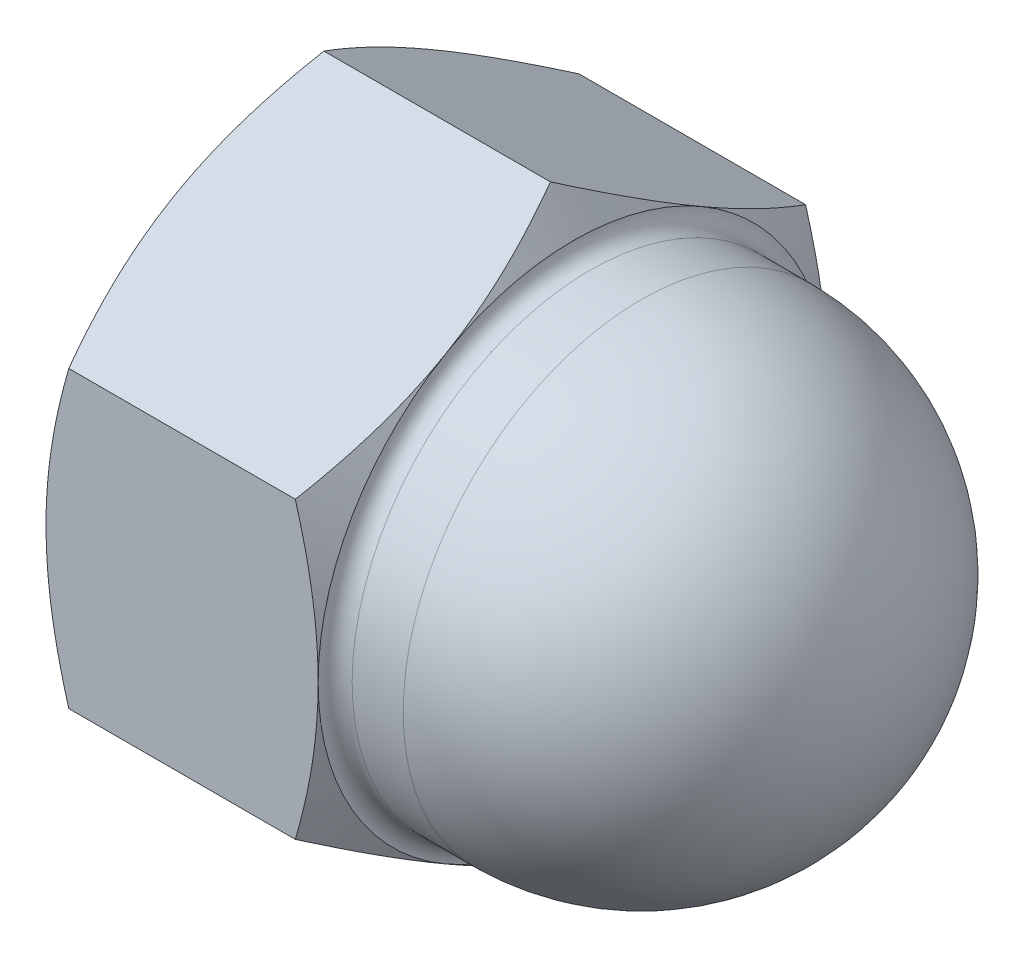
SolidWorks part; units mm, degrees
extrude "BaseNut" add sketch "BaseNutSke" along normal blind 16
sketch "BaseNutSke" plane through (0, 0, 0) normal (1, 0, 0) x (0, 0, -1)
  line L6 (15, 8.6603) -> (15, -8.6603)
  line L7 (-15, 8.6603) -> (-15, -8.6603)
  line L8 (15, 8.6603) -> (0, 17.3205)
  line L9 (0, 17.3205) -> (-15, 8.6603)
  line L10 (-15, -8.6603) -> (0, -17.3205)
  line L11 (0, -17.3205) -> (15, -8.6603)
  dimension "D4" = 60
  dimension "D1" = 120
  dimension "D2" = 15
  dimension "D3" = 15
  dimension "Width_flats" = 30
revolve "DoubleChamfer" cut sketch "Sketch4" angle 360 about L10 other way angle 118
sketch "Sketch4" plane through (0, 0, 0) normal (0, 0, 1) x (1, 0, 0)
  line L0 (0, 15) -> (2.7831, 19.8205)
  line L1 (16, 15) -> (13.2169, 19.8205)
  line L2 (2.7831, 19.8205) -> (13.2169, 19.8205)
  line L3 (16, 15) -> (18, 15)
  line L4 (18, 15) -> (18, 30)
  line L5 (18, 30) -> (-2, 30)
  line L6 (0, 15) -> (-2, 15)
  line L7 (-2, 15) -> (-2, 30)
  line L8 (16, 17.3205) -> (16, 8.6603) construction
  line L9 (0, 17.3205) -> (0, 8.6603) construction
  line L10 (0, 0) -> (57.15, 0) construction
  line L11 (16, 17.3205) -> (0, 17.3205) construction
  point P17 (16, 15)
  dimension "D1" = 30
  dimension "D2" = 30
  dimension "D3" = 2
  dimension "D4" = 2
  dimension "D5" = 2.5
  dimension "D6" = 15
  dimension "D7" = 15
revolve "TapDrill" cut sketch "TapDriSke"
sketch "TapDriSke" plane through (0, 0, 0) normal (0, 0, 1) x (1, 0, 0)
  line L0 (0, 0) -> (44.45, 0) construction
  line L1 (0, 8.75) -> (23, 8.75)
  line L2 (0, 12.9904) -> (0, 0) construction
  line L3 (23, 8.75) -> (28.2575, 0)
  line L4 (0, 0) -> (63.5, 0) construction
  line L5 (28.2575, 0) -> (0, 0)
  line L6 (0, 0) -> (0, 8.75)
  line L7 (23, -8.75) -> (28.2575, 0) construction
  line L8 (0, -8.75) -> (23, -8.75) construction
  line L9 (2.5, 6.35) -> (2.5, 3.175) construction
  dimension "Drill_depth" = 23
cosmetic thread "ThreadCosmetic" [suppressed]
revolve "EndChamfer" cut sketch "EndChamferSketch" angle 360 about L4
sketch "EndChamferSketch" plane through (0, 0, 0) normal (0, 0, 1) x (1, 0, 0)
  line L0 (-0.0254, 10) -> (0.0254, 10)
  line L1 (0.0254, 10) -> (0.9882, 8.625)
  line L2 (0.9882, 8.625) -> (-0.0254, 8.625)
  line L3 (-0.0254, 8.625) -> (-0.0254, 10)
  line L4 (0, 0) -> (-15.875, 0) construction
  dimension "D1" = 0.0508
  dimension "D2" = 35
  dimension "D3" = 0.0254
  dimension "ChamferDepth" = 1.375
  dimension "ThreadMajor" = 10
revolve "Undercut" cut sketch "UcutSke" angle 360 about L0 other way angle 70
sketch "UcutSke" plane through (0, 0, 0) normal (0, 0, 1) x (1, 0, 0)
  line L0 (0, 0) -> (38.1, 0) construction
  line L1 (17.8994, 10.1) -> (17.12, 8.75)
  line L2 (17.12, 0.25) -> (26.42, 0.25)
  line L3 (26.42, 0.25) -> (26.42, 10.1)
  line L4 (26.42, 10.1) -> (17.8994, 10.1)
  line L5 (17.12, 0.25) -> (17.12, 8.75)
  line L6 (23, 8.75) -> (0, 8.75) construction
  line L7 (0, 12.9904) -> (0, 0) construction
  dimension "D1" = 0.5
  dimension "D2" = 240
ref_plane "Plane1" through (0, 0, 0) normal (0, 0, 1) x (1, 0, 0)
ref_plane "Plane2" through (0, 0, 0) normal (0, 1, 0) x (1, 0, 0)
ref_plane "Plane3" through (0, 0, 0) normal (1, 0, 0) x (0, 0, -1)
sketch "DomeSke" plane through (0, 0, 0) normal (0, 0, 1) x (1, 0, 0)
  line L0 (0, 0) -> (63.5, 0) construction
  line L1 (0, 8.6603) -> (0, -8.6603) construction
  line L2 (34, 0) -> (0, 0)
  line L3 (0, 14) -> (20, 14)
  line L4 (0, -14) -> (22.225, -14) construction
  line L5 (0, 14) -> (0, 0)
  arc A0 (20, 14) -> (34, 0) centre (20, 0) cw
revolve "Dome" add sketch "DomeSke" angle 360 about L0
sketch "ThdSchSke" plane through (0, 0, 0) normal (0, 1, 0) x (1, 0, 0)
  line L0 (0.0381, 10) -> (-0.8372, 8.75)
  line L1 (-0.8372, 8.75) -> (-0.8372, 4.375)
  line L2 (-0.8372, 4.375) -> (0.9134, 4.375)
  line L3 (0.9134, 4.375) -> (0.9134, 8.75)
  line L4 (0.9134, 8.75) -> (0.0381, 10)
  line L5 (-38.1, 0) -> (3.175, 0) construction
  line L6 (0, 0) -> (-15.875, 0) construction
  line L7 (0, 0) -> (63.5, 0) construction
  line L9 (2.5381, 0.475) -> (2.5381, -5.875) construction
  dimension "D1" = 0.0381
  dimension "Thread_major" = 20
  dimension "Tap_drill" = 17.5
  dimension "OverCut" = 8.75
revolve "ThreadSchematic" [suppressed] cut sketch "ThdSchSke" angle 360 about L5
pattern_linear "ThdSchPat" [suppressed]
fillet "DomeFillet" radius 1 1 edges at (16, 0, 14)
equation "' \"Width_flats@BaseNutSke\" = 30"
equation "' \"Hex_ht@BaseNut\" = 16"
equation "' \"Overall_ht@DomeSke\" = 34"
equation "' \"Dome_rad@DomeSke\" = 14"
equation "' \"Thread_min@TapDriSke\" = 17.5"
equation "' \"Drill_clr@TapDriSke\" = 5.0"
equation "' \"Advance@ThdSchSke\" = 2.5"
equation "' \"Thread_nominal@ThreadCosmetic\" = 20"
equation "' \"Radius@DomeFillet\" = 0.5"
equation "' \"Ucut_wid@UcutSke\" = 9.3"
equation "' \"Ucut_dep@UcutSke\" = 26.42"
equation "\"Drill_depth@TapDriSke\" = \"Overall_ht@DomeSke\"  - \"Drill_clr@TapDriSke\" - 0.3 * \"Thread_nominal@ThreadCosmetic\""
equation "\"Ucut_dia@UcutSke\" = \"Thread_nominal@ThreadCosmetic\" * 1.01"
equation "\"Thread_depth@ThreadCosmetic\" = \"Ucut_dep@UcutSke\" - \"Ucut_wid@UcutSke\" + ( \"Thread_nominal@ThreadCosmetic\" - \"Thread_min@TapDriSke\" ) / 2 * 0.57735"
equation "\"D2@BaseNutSke\" = \"Width_flats@BaseNutSke\" / 2"
equation "\"D3@BaseNutSke\" = \"Width_flats@BaseNutSke\" / 2"
equation "\"D7@Sketch4\" = \"Width_flats@BaseNutSke\" / 2"
equation "\"D5@Sketch4\" = \"Width_flats@BaseNutSke\" / 12"
equation "\"Thread_major@ThdSchSke\" = \"Thread_nominal@ThreadCosmetic\""
equation "\"Tap_drill@ThdSchSke\" = \"Thread_min@TapDriSke\""
equation "\"OverCut@ThdSchSke\" = \"Tap_drill@ThdSchSke\" * 0.5"
equation "\"Num_threads@ThdSchPat\" = int(  ( \"Thread_depth@ThreadCosmetic\" - 0.002 ) / \"Advance@ThdSchSke\" + 0.999 )  + 1"
equation "\"Advance@ThdSchPat\" = ( \"Thread_depth@ThreadCosmetic\" - 0.002 ) /  (\"Num_threads@ThdSchPat\" - 1) 'relax it"
equation "\"ThreadMajor@EndChamferSketch\" = \"Thread_nominal@ThreadCosmetic\" * 0.5"
equation "\"ChamferDepth@EndChamferSketch\" = (\"Thread_nominal@ThreadCosmetic\" - \"Thread_min@TapDriSke\") * 0.55"
